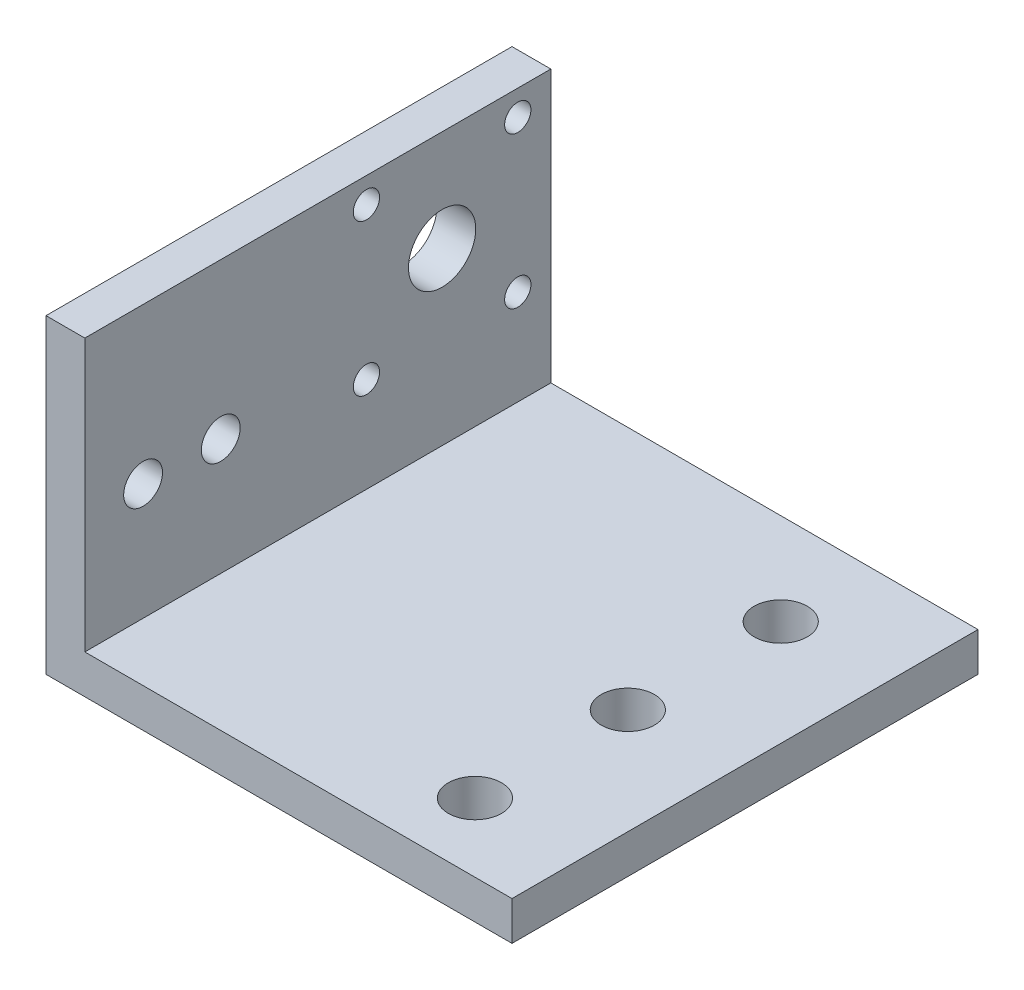
SolidWorks part; units mm, degrees
material "6061 Alloy"
ref_plane "Front Plane" through (0, 0, 0) normal (0, 0, 1) x (1, 0, 0)
ref_plane "Top Plane" through (0, 0, 0) normal (0, 1, 0) x (1, 0, 0)
ref_plane "Right Plane" through (0, 0, 0) normal (1, 0, 0) x (0, 0, -1)
sketch "Sketch1" plane through (0, 0, 0) normal (0, 0, 1) x (1, 0, 0)
  line L0 (-35.999, 18.8304) -> (-35.999, -25.6196)
  line L1 (-35.999, -25.6196) -> (33.851, -25.6196)
  line L2 (-42.349, 18.8304) -> (-42.349, -31.9696)
  line L3 (-42.349, -31.9696) -> (33.851, -31.9696)
  line L4 (-42.349, 18.8304) -> (-35.999, 18.8304)
  line L5 (33.851, -25.6196) -> (33.851, -31.9696)
  dimension "D2" = 50.8
  dimension "D3" = 76.2
  dimension "D1" = 6.35
extrude "Boss-Extrude1" add sketch "Sketch1" along normal blind 76.2
sketch "Sketch2" plane through (-35.999, 0, 0) normal (1, 0, 0) x (0, 0, -1)
  line L0 (-76.2, -25.6196) -> (0, -25.6196) construction
  line L1 (0, -25.6196) -> (0, 18.8304) construction
  circle A0 centre (-17.78, 2.3204) radius 5.5
  dimension "D1" = 27.94
  dimension "D2" = 17.78
  dimension "D3" = 11
hole_wizard "M4 Clearance Hole1" positions "Sketch5" profile "Sketch3" hole size "M4" standard "ANSI Metric" end condition up to next
sketch "Sketch5" plane through (-35.999, 0, 0) normal (1, 0, 0) x (0, 0, -1)
  line L2 (-30.1548, -10.0544) -> (-5.4052, -10.0544)
  line L3 (-30.1548, -10.0544) -> (-30.1548, 14.6952)
  line L4 (-30.1548, 14.6952) -> (-5.4052, 14.6952)
  line L5 (-5.4052, -10.0544) -> (-5.4052, 14.6952)
  line L6 (-30.1548, -10.0544) -> (-5.4052, 14.6952) construction
  line L7 (-30.1548, 14.6952) -> (-5.4052, -10.0544) construction
  circle A1 centre (-17.78, 2.3204) radius 17.5006
  point P0 (-30.1548, 14.6952)
  point P2 (-30.1548, -10.0544)
  point P4 (-5.4052, -10.0544)
  point P6 (-5.4052, 14.6952)
  dimension "D1" = 35.0012
sketch "Sketch3" plane through (-35.999, 14.6952, 30.1548) normal (0, 1, 0) x (0, 0, -1)
  line L0 (0, 0) -> (0, 6.35)
  line L1 (0, 6.35) -> (2.15, 6.35)
  line L2 (2.15, 6.35) -> (2.15, 0)
  line L5 (2.15, 0) -> (0, 0)
  line L11 (0, -6.35) -> (0, 107.95) construction
  dimension "Thru Hole Dia." = 4.3
  dimension "Thru Hole Depth" = 6.35
extrude "Cut-Extrude1" cut sketch "Sketch2" against normal blind 8.636 contours A0
sketch "Sketch6" plane through (0, -31.9696, 0) normal (0, -1, 0) x (1, 0, 0)
  line L2 (33.851, 76.2) -> (33.851, 0) construction
  line L3 (-42.349, 38.1) -> (33.851, 38.1) construction
  line L4 (-42.349, 76.2) -> (-42.349, 0) construction
  circle A0 centre (16.5913, 65) radius 4.35
  circle A1 centre (16.5913, 15) radius 4.35
  circle A3 centre (16.5913, 40) radius 4.35
  circle A6 centre (16.5913, 15) radius 4.35 construction
  circle A8 centre (16.5913, 40) radius 4.35 construction
  circle A9 centre (16.5913, 65) radius 4.35 construction
  dimension "D1" = 8.7
  dimension "D2" = 8.7
  dimension "D4" = 8.7
extrude "Cut-Extrude2" cut sketch "Sketch6" against normal blind 13.97
sketch "Sketch7" plane through (-42.349, 0, 0) normal (-1, 0, 0) x (0, 0, 1)
  line L0 (76.2, -31.9696) -> (0, -31.9696) construction
  line L1 (76.2, 18.8304) -> (76.2, -31.9696) construction
  circle A0 centre (53.975, -6.5696) radius 3.175
  circle A1 centre (66.675, -6.5696) radius 3.175
  dimension "D3" = 6.35
  dimension "D4" = 9.525
  dimension "D1" = 25.4
  dimension "D2" = 25.4
  dimension "D5" = 22.225
extrude "Cut-Extrude3" cut sketch "Sketch7" against normal up to next
